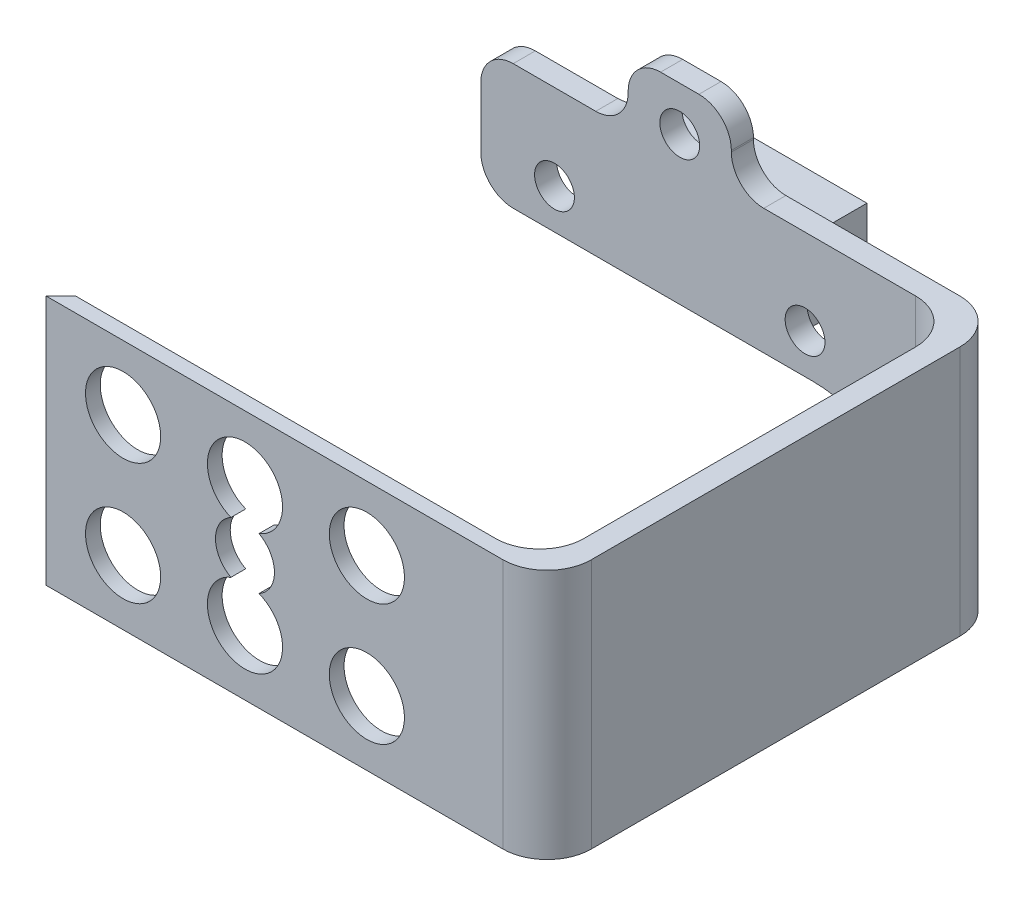
SolidWorks part; units mm, degrees
ref_plane "前视基准面" through (0, 0, 0) normal (0, 0, 1) x (1, 0, 0)
ref_plane "上视基准面" through (0, 0, 0) normal (0, 1, 0) x (1, 0, 0)
ref_plane "右视基准面" through (0, 0, 0) normal (1, 0, 0) x (0, 0, -1)
sketch "草图1" plane through (0, 0, 0) normal (0, 0, 1) x (1, 0, 0)
  line L1 (-13.5, -8.5) -> (13.5, -8.5)
  line L2 (-13.5, -8.5) -> (-13.5, 8.5)
  line L3 (-13.5, 8.5) -> (13.5, 8.5)
  line L4 (13.5, -8.5) -> (13.5, 8.5)
  line L5 (-13.5, -8.5) -> (13.5, 8.5) construction
  line L6 (-13.5, 8.5) -> (13.5, -8.5) construction
  point P0 (0, 0)
  dimension "D1" = 27
  dimension "D2" = 17
extrude "凸台-拉伸1" add sketch "草图1" along normal blind 1
sketch "草图2" plane through (0, 0, 1) normal (0, 0, 1) x (1, 0, 0)
  line L0 (-8.27, 4.125) -> (8.27, 4.125) construction
  line L3 (0, 1.575) -> (0, -1.575) construction
  line L4 (8.27, 4.125) -> (8.27, -4.125) construction
  line L5 (8.27, -4.125) -> (-8.27, -4.125) construction
  line L6 (-8.27, -4.125) -> (-8.27, 4.125) construction
  circle A0 centre (0, 4.125) radius 2.55
  circle A1 centre (0, -4.125) radius 2.55
  circle A2 centre (8.27, 4.125) radius 2.55
  circle A3 centre (8.27, -4.125) radius 2.55
  circle A4 centre (-8.27, 4.125) radius 2.55
  circle A5 centre (-8.27, -4.125) radius 2.55
  point P2 (0, 1.575)
  point P5 (0, -1.575)
  point P6 (0, 0)
  point P11 (-2.55, 4.125)
  point P20 (-5.72, 4.125)
  dimension "D1" = 5.1
  dimension "D4" = 3.17
  dimension "D2" = 3.15
extrude "切除-拉伸1" cut sketch "草图2" against normal through all
sketch "草图3" plane through (0, -8.5, 0) normal (0, -1, 0) x (1, 0, 0)
  line L0 (13.5, 0) -> (19, 0)
  line L1 (13.5, 1) -> (13.5, 0)
  line L2 (20.5, 1) -> (13.5, 1)
  line L3 (20.5, 1) -> (20.5, -30)
  line L4 (-13.5, 1) -> (-13.5, 0) construction
  line L5 (19, -28.5) -> (19, 0)
  line L6 (-13.5, -28.5) -> (-13.5, -30)
  line L7 (-13.5, -30) -> (20.5, -30)
  line L9 (-13.5, -28.5) -> (19, -28.5)
  dimension "D1" = 7
  dimension "D2" = 1.5
  dimension "D3" = 1.5
  dimension "D4" = 30
extrude "凸台-拉伸2" add sketch "草图3" against normal up to surface (17 mm away) up to face at (0, 8.5, 0.5)
sketch "草图6" plane through (0, 0, 0) normal (0, 1, 0) x (1, 0, 0)
  line L0 (19, 0) -> (19, 5)
  line L1 (19, 28.5) -> (19, 0) construction
  line L2 (19, 5) -> (14, 0)
  line L3 (19, 0) -> (-13.5, 0) construction
  line L4 (14, 0) -> (19, 0)
  line L5 (19, 28.5) -> (14, 28.5)
  line L6 (-13.5, 28.5) -> (19, 28.5) construction
  line L7 (14, 28.5) -> (19, 23.5)
  line L8 (19, 23.5) -> (19, 28.5)
  line L9 (20.5, 30) -> (-13.5, 30) construction
  line L10 (19, 19) -> (17.5, 19)
  line L11 (19, 19) -> (19, 21)
  line L12 (19, 21) -> (17.5, 21)
  line L13 (17.5, 19) -> (17.5, 21)
  point P18 (17.5, 20)
  dimension "D1" = 5
  dimension "D2" = 5
  dimension "D3" = 5
  dimension "D4" = 5
  dimension "D5" = 10
  dimension "D6" = 1.5
  dimension "D7" = 2
extrude "凸台-拉伸3" add sketch "草图6" along normal mid plane 4
chamfer "倒角1" distance 1 angle 45 1 edges at (-13.5, 0, 0)
sketch "草图8" plane through (0, 0, 0) normal (0, 0, -1) x (-1, 0, 0)
  circle A0 centre (0, 0) radius 2
  dimension "D1" = 4
extrude "切除-拉伸4" cut sketch "草图8" against normal up to next
fillet "圆角1" radius 3 6 edges at (20.5, 0, -30) (20.5, 0, 1) (19, 5.25, 0) (19, -5.25, 0) (19, 5.25, -28.5) (19, -5.25, -28.5)
sketch "草图9" plane through (0, 0, -30) normal (0, 0, -1) x (-1, 0, 0)
  line L1 (-3.5, 13) -> (3.5, 13)
  line L2 (-3.5, 13) -> (-3.5, 0)
  line L3 (-3.5, 0) -> (3.5, 0)
  line L4 (3.5, 13) -> (3.5, 0)
  point P4 (0, 0)
  dimension "D1" = 7
  dimension "D2" = 13
extrude "凸台-拉伸4" add sketch "草图9" against normal up to surface (1.5 mm away) up to face at (8.125, 0, -28.5)
sketch "草图7" plane through (0, 0, -30) normal (0, 0, -1) x (-1, 0, 0)
  line L0 (0, 0) -> (0, 10) construction
  line L1 (-8.5, 2.7) -> (8.5, 2.7) construction
  circle A0 centre (0, 0) radius 1.35 construction
  circle A1 centre (0, 10) radius 1.35
  circle A3 centre (-8.5, 2.7) radius 1.35
  circle A4 centre (8.5, 2.7) radius 1.35
  point P9 (0, 2.7)
  dimension "D1" = 2.7
  dimension "D5" = 2.7
  dimension "D6" = 2.7
  dimension "D2" = 10
  dimension "D3" = 2.7
  dimension "D4" = 17
extrude "切除-拉伸5" cut sketch "草图7" against normal blind 10
sketch "草图11" plane through (0, 0, -30) normal (0, 0, -1) x (-1, 0, 0)
  line L2 (13.5, 0) -> (-17.5, 0)
  line L3 (13.5, 8.5) -> (13.5, -8.5) construction
  line L4 (-17.5, 8.5) -> (-17.5, -8.5) construction
  line L5 (-17.5, 0) -> (-17.5, -8.5)
  line L6 (-17.5, -8.5) -> (13.5, -8.5)
  line L7 (13.5, -8.5) -> (13.5, 0)
  arc A1 (-17.5, -8.5) -> (-9, 0) centre (-9, -8.5) cw
  line M4 (13.5, -8.5) -> (13.5, 8.5)
  line M16 (-17.5, -8.5) -> (13.5, -8.5)
extrude "切除-拉伸6" cut sketch "草图11" against normal up to next contours A1 L2 M16 M4 region at (1.1496, -4.397, -30)
fillet "圆角2" radius 2.2 6 edges at (-13.5, 8.5, -29.25) (-3.5, 8.5, -29.25) (3.5, 8.5, -29.25) (-3.5, 13, -29.25) (3.5, 13, -29.25) (-13.5, 0, -29.25)
sketch "草图13" plane through (0, 0, -30) normal (0, 0, -1) x (-1, 0, 0)
  line L0 (11.3, 0) -> (-9, 0) construction
  line L1 (-11.2, 5.4) -> (-5.8, 5.4)
  line L2 (-11.2, 5.4) -> (-11.2, 0)
  line L3 (-11.2, 0) -> (-5.8, 0)
  line L4 (-5.8, 5.4) -> (-5.8, 0)
  line L5 (-11.2, 5.4) -> (-5.8, 0) construction
  line L6 (-11.2, 0) -> (-5.8, 5.4) construction
  line L11 (11.2, 0) -> (5.8, 0)
  line L12 (11.2, 0) -> (11.2, 5.4)
  line L18 (-5.8, 5.4) -> (5.8, 5.4)
  line L19 (11.2, 5.4) -> (5.8, 5.4)
  line L20 (5.8, 0) -> (5.8, 5.4)
  line L21 (11.2, 0) -> (5.8, 5.4) construction
  line L22 (11.2, 5.4) -> (5.8, 0) construction
  line L23 (-5.8, 5.4) -> (-5.8, 0)
  line L24 (-5.8, 0) -> (5.8, 0)
  line L25 (5.8, 5.4) -> (5.8, 0)
  point P0 (-8.5, 2.7)
  point P6 (8.5, 2.7)
  point P12 (0.1939, 2.7)
  line M20 (-9, 0) -> (11.3, 0)
extrude "凸台-拉伸6" add sketch "草图13" along normal blind 5.4 contours L20 L18 L4 M20 region at (0, 2.7, -30)
